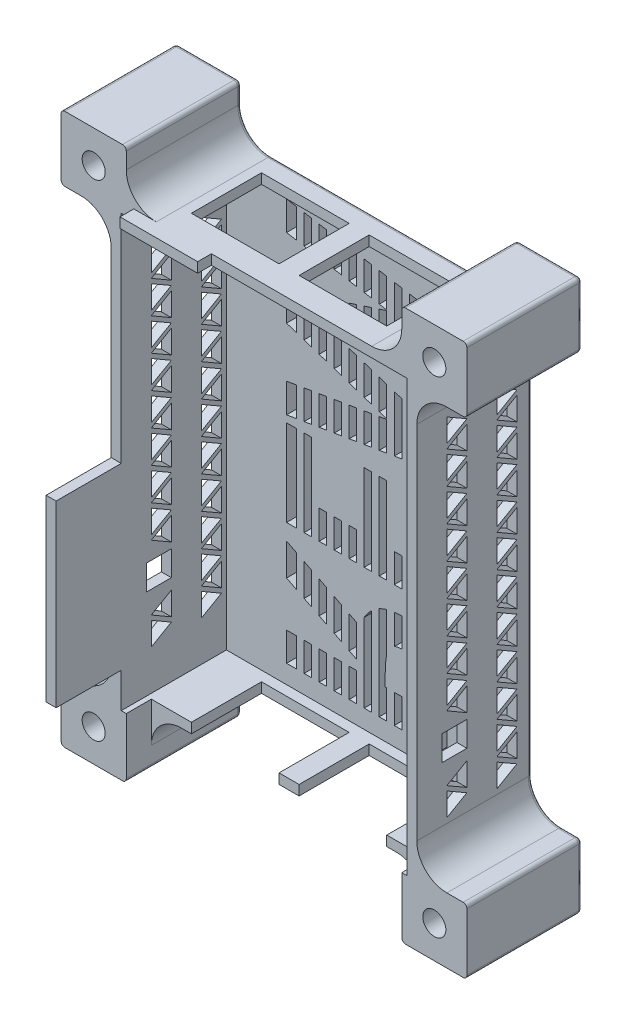
SolidWorks part; units mm, degrees
ref_plane "Front Plane" through (0, 0, 0) normal (0, 0, 1) x (1, 0, 0)
ref_plane "Top Plane" through (0, 0, 0) normal (0, 1, 0) x (1, 0, 0)
ref_plane "Right Plane" through (0, 0, 0) normal (1, 0, 0) x (0, 0, -1)
sketch "Sketch1" plane through (0, 0, 0) normal (0, 0, 1) x (1, 0, 0)
  line L1 (0, 0) -> (61, 0)
  line L2 (0, 0) -> (0, 90)
  line L3 (0, 90) -> (61, 90)
  line L4 (61, 0) -> (61, 90)
  dimension "D1" = 90
  dimension "D2" = 61
extrude "Boss-Extrude1" add sketch "Sketch1" along normal blind 4
sketch "Sketch2" plane through (0, 0, 4) normal (0, 0, 1) x (1, 0, 0)
  line L0 (61, 90) -> (0, 90) construction
  line L1 (2, 88) -> (59, 88)
  line L2 (2, 88) -> (2, 2)
  line L3 (2, 2) -> (59, 2)
  line L4 (59, 88) -> (59, 2)
  line L5 (2.2, 0) -> (-2.2, 0) construction
  line L6 (0, -2.2) -> (0, 2.2) construction
  line L7 (61, 0) -> (61, 90) construction
  dimension "D1" = 2
  dimension "D2" = 2
  dimension "D3" = 2
  dimension "D4" = 2
extrude "Cut-Extrude1" cut sketch "Sketch2" against normal blind 2
sketch "Sketch3" plane through (0, 0, 4) normal (0, 0, 1) x (1, 0, 0)
  line L8 (2, 88) -> (2, 2)
  line L9 (2, 2) -> (59, 2)
  line L10 (59, 2) -> (59, 88)
  line L11 (59, 88) -> (2, 88)
  line L12 (2, 88) -> (2, 2)
  line L13 (2, 2) -> (59, 2)
  line L14 (59, 2) -> (59, 88)
  line L15 (59, 88) -> (2, 88)
  line L26 (0, 90) -> (0, 0)
  line L27 (0, 0) -> (61, 0)
  line L28 (61, 0) -> (61, 90)
  line L29 (61, 90) -> (0, 90)
  line L30 (0, 90) -> (0, 0)
  line L31 (0, 0) -> (61, 0)
  line L32 (61, 0) -> (61, 90)
  line L33 (61, 90) -> (0, 90)
  dimension "D1" = 2
  dimension "D2" = 0
extrude "Boss-Extrude2" add sketch "Sketch3" along normal blind 14
sketch "Sketch4" plane through (0, 0, 18) normal (0, 0, 1) x (1, 0, 0)
  line L2 (9.9, 0) -> (-9.9, 0) construction
  line L3 (0, -9.9) -> (0, 9.9) construction
  line L4 (61, 0) -> (61, 90) construction
  line L10 (0, 90) -> (0, 0) construction
  line L12 (2, 88) -> (2, 2) construction
  line L13 (2, 88) -> (2, 2) construction
  line L14 (2, 2) -> (2, 88)
  line L15 (59, 88) -> (2, 88) construction
  line L16 (59, 88) -> (2, 88) construction
  line L49 (59, 88) -> (2, 88)
  line L50 (59, 2) -> (59, 88)
  line L52 (0, 90) -> (0, 2)
  line L53 (61, 90) -> (0, 90)
  line L54 (61, 2) -> (61, 90)
  line L55 (59, 2) -> (61, 2)
  line L56 (2, 2) -> (0, 2)
  dimension "D2" = 2
  dimension "D3" = 2
  dimension "D1" = 2
extrude "Boss-Extrude3" add sketch "Sketch4" along normal blind 5
sketch "Sketch5" plane through (0, 0, 0) normal (0, -1, 0) x (-1, 0, 0)
  line L0 (0, -18) -> (-61, -18) construction
  line L1 (-11, -18) -> (-28.5, -18)
  line L2 (-11, -18) -> (-11, -4)
  line L3 (-11, -4) -> (-28.5, -4)
  line L4 (-28.5, -18) -> (-28.5, -4)
  line L5 (0, 9.9) -> (0, -9.9) construction
  line L6 (-32.5, -18) -> (-50, -18)
  line L7 (-32.5, -18) -> (-32.5, -4)
  line L8 (-32.5, -4) -> (-50, -4)
  line L9 (-50, -18) -> (-50, -4)
  dimension "D1" = 14
  dimension "D2" = 14
  dimension "D3" = 17.5
  dimension "D4" = 17.5
  dimension "D5" = 4
  dimension "D6" = 11
extrude "Cut-Extrude2" cut sketch "Sketch5" against normal blind 5
sketch "Sketch6" plane through (0, 90, 0) normal (0, 1, 0) x (1, 0, 0)
  line L2 (50, -18) -> (50, -4)
  line L3 (50, -4) -> (32.5, -4)
  line L4 (32.5, -18) -> (32.5, -4)
  line L5 (61, 0) -> (0, 0) construction
  line L7 (28.5, -18) -> (28.5, -4)
  line L8 (28.5, -4) -> (11, -4)
  line L9 (11, -18) -> (11, -4)
  line L10 (61, -23) -> (61, 0) construction
  line L12 (11, -18) -> (28.5, -18)
  line L13 (32.5, -18) -> (50, -18)
  dimension "D1" = 4
  dimension "D2" = 4
  dimension "D3" = 4
  dimension "D4" = 17.5
  dimension "D5" = 17.5
  dimension "D6" = 11
  dimension "D7" = 14
  dimension "D8" = 14
extrude "Cut-Extrude3" cut sketch "Sketch6" against normal blind 5
sketch "Sketch7" plane through (0, 0, 23) normal (0, 0, 1) x (1, 0, 0)
  line L0 (0, 90) -> (0, 2) construction
  line L1 (0, 9) -> (2, 9)
  line L2 (0, 9) -> (0, 44.75)
  line L3 (0, 44.75) -> (2, 44.75)
  line L4 (2, 9) -> (2, 44.75)
  line L5 (2, 2) -> (2, 88) construction
  line L6 (0, 2) -> (2, 2) construction
  dimension "D1" = 7
  dimension "D2" = 35.75
extrude "Boss-Extrude4" add sketch "Sketch7" along normal blind 13
sketch "Sketch8" plane through (61, 0, 0) normal (1, 0, 0) x (0, 0, -1)
  line L0 (-13, 17.852) -> (-13, 13.2332)
  line L5 (-13, 13.2332) -> (-17, 15.5426)
  line L6 (-17, 15.5426) -> (-13, 17.852)
  line L8 (-13, 20) -> (-18, 20)
  line L9 (-13, 20) -> (-13, 25)
  line L10 (-13, 25) -> (-18, 25)
  line L11 (-18, 20) -> (-18, 25)
  line L23 (-18, 0) -> (0, 0) construction
  line L24 (0, 0) -> (0, 90) construction
  line L25 (-3, 12.3094) -> (-7, 10)
  line L26 (-7, 10) -> (-7, 14.6188)
  line L27 (-7, 14.6188) -> (-3, 12.3094)
  line L28 (-3, 13.2332) -> (-7, 15.5426)
  line L29 (-7, 15.5426) -> (-3, 17.852)
  line L30 (-3, 17.852) -> (-3, 13.2332)
  line L31 (-17, 14.6188) -> (-13, 12.3094)
  line L32 (-13, 12.3094) -> (-17, 10)
  line L33 (-17, 10) -> (-17, 14.6188)
  line L40 (-13, 30.7846) -> (-13, 26.1658)
  line L41 (-13, 26.1658) -> (-17, 28.4752)
  line L42 (-17, 28.4752) -> (-13, 30.7846)
  line L46 (-13, 37.2509) -> (-13, 32.6321)
  line L47 (-13, 32.6321) -> (-17, 34.9415)
  line L48 (-17, 34.9415) -> (-13, 37.2509)
  line L49 (-17, 34.0178) -> (-13, 31.7084)
  line L50 (-13, 31.7084) -> (-17, 29.399)
  line L51 (-17, 29.399) -> (-17, 34.0178)
  line L52 (-13, 43.7173) -> (-13, 39.0985)
  line L53 (-13, 39.0985) -> (-17, 41.4079)
  line L54 (-17, 41.4079) -> (-13, 43.7173)
  line L55 (-17, 40.4841) -> (-13, 38.1747)
  line L56 (-13, 38.1747) -> (-17, 35.8653)
  line L57 (-17, 35.8653) -> (-17, 40.4841)
  line L58 (-13, 50.1836) -> (-13, 45.5648)
  line L59 (-13, 45.5648) -> (-17, 47.8742)
  line L60 (-17, 47.8742) -> (-13, 50.1836)
  line L61 (-17, 46.9504) -> (-13, 44.641)
  line L62 (-13, 44.641) -> (-17, 42.3316)
  line L63 (-17, 42.3316) -> (-17, 46.9504)
  line L64 (-13, 56.6499) -> (-13, 52.0311)
  line L65 (-13, 52.0311) -> (-17, 54.3405)
  line L66 (-17, 54.3405) -> (-13, 56.6499)
  line L67 (-17, 53.4167) -> (-13, 51.1073)
  line L68 (-13, 51.1073) -> (-17, 48.7979)
  line L69 (-17, 48.7979) -> (-17, 53.4167)
  line L70 (-13, 63.1162) -> (-13, 58.4974)
  line L71 (-13, 58.4974) -> (-17, 60.8068)
  line L72 (-17, 60.8068) -> (-13, 63.1162)
  line L73 (-17, 59.8831) -> (-13, 57.5737)
  line L74 (-13, 57.5737) -> (-17, 55.2643)
  line L75 (-17, 55.2643) -> (-17, 59.8831)
  line L76 (-13, 69.5825) -> (-13, 64.9637)
  line L77 (-13, 64.9637) -> (-17, 67.2731)
  line L78 (-17, 67.2731) -> (-13, 69.5825)
  line L79 (-17, 66.3494) -> (-13, 64.04)
  line L80 (-13, 64.04) -> (-17, 61.7306)
  line L81 (-17, 61.7306) -> (-17, 66.3494)
  line L82 (-13, 76.0489) -> (-13, 71.4301)
  line L83 (-13, 71.4301) -> (-17, 73.7395)
  line L84 (-17, 73.7395) -> (-13, 76.0489)
  line L85 (-17, 72.8157) -> (-13, 70.5063)
  line L86 (-13, 70.5063) -> (-17, 68.1969)
  line L87 (-17, 68.1969) -> (-17, 72.8157)
  line L91 (-17, 79.282) -> (-13, 76.9726)
  line L92 (-13, 76.9726) -> (-17, 74.6632)
  line L93 (-17, 74.6632) -> (-17, 79.282)
  line L94 (-3, 24.3183) -> (-3, 19.6995)
  line L95 (-3, 19.6995) -> (-7, 22.0089)
  line L96 (-7, 22.0089) -> (-3, 24.3183)
  line L97 (-7, 21.0851) -> (-3, 18.7757)
  line L98 (-3, 18.7757) -> (-7, 16.4663)
  line L99 (-7, 16.4663) -> (-7, 21.0851)
  line L100 (-3, 30.7846) -> (-3, 26.1658)
  line L101 (-3, 26.1658) -> (-7, 28.4752)
  line L102 (-7, 28.4752) -> (-3, 30.7846)
  line L103 (-7, 27.5514) -> (-3, 25.242)
  line L104 (-3, 25.242) -> (-7, 22.9326)
  line L105 (-7, 22.9326) -> (-7, 27.5514)
  line L106 (-3, 37.2509) -> (-3, 32.6321)
  line L107 (-3, 32.6321) -> (-7, 34.9415)
  line L108 (-7, 34.9415) -> (-3, 37.2509)
  line L109 (-7, 34.0178) -> (-3, 31.7084)
  line L110 (-3, 31.7084) -> (-7, 29.399)
  line L111 (-7, 29.399) -> (-7, 34.0178)
  line L112 (-3, 43.7173) -> (-3, 39.0985)
  line L113 (-3, 39.0985) -> (-7, 41.4079)
  line L114 (-7, 41.4079) -> (-3, 43.7173)
  line L115 (-7, 40.4841) -> (-3, 38.1747)
  line L116 (-3, 38.1747) -> (-7, 35.8653)
  line L117 (-7, 35.8653) -> (-7, 40.4841)
  line L118 (-3, 50.1836) -> (-3, 45.5648)
  line L119 (-3, 45.5648) -> (-7, 47.8742)
  line L120 (-7, 47.8742) -> (-3, 50.1836)
  line L121 (-7, 46.9504) -> (-3, 44.641)
  line L122 (-3, 44.641) -> (-7, 42.3316)
  line L123 (-7, 42.3316) -> (-7, 46.9504)
  line L124 (-3, 56.6499) -> (-3, 52.0311)
  line L125 (-3, 52.0311) -> (-7, 54.3405)
  line L126 (-7, 54.3405) -> (-3, 56.6499)
  line L127 (-7, 53.4167) -> (-3, 51.1073)
  line L128 (-3, 51.1073) -> (-7, 48.7979)
  line L129 (-7, 48.7979) -> (-7, 53.4167)
  line L130 (-3, 63.1162) -> (-3, 58.4974)
  line L131 (-3, 58.4974) -> (-7, 60.8068)
  line L132 (-7, 60.8068) -> (-3, 63.1162)
  line L133 (-7, 59.8831) -> (-3, 57.5737)
  line L134 (-3, 57.5737) -> (-7, 55.2643)
  line L135 (-7, 55.2643) -> (-7, 59.8831)
  line L136 (-3, 69.5825) -> (-3, 64.9637)
  line L137 (-3, 64.9637) -> (-7, 67.2731)
  line L138 (-7, 67.2731) -> (-3, 69.5825)
  line L139 (-7, 66.3494) -> (-3, 64.04)
  line L140 (-3, 64.04) -> (-7, 61.7306)
  line L141 (-7, 61.7306) -> (-7, 66.3494)
  line L142 (-3, 76.0489) -> (-3, 71.4301)
  line L143 (-3, 71.4301) -> (-7, 73.7395)
  line L144 (-7, 73.7395) -> (-3, 76.0489)
  line L145 (-7, 72.8157) -> (-3, 70.5063)
  line L146 (-3, 70.5063) -> (-7, 68.1969)
  line L147 (-7, 68.1969) -> (-7, 72.8157)
  line L151 (-7, 79.282) -> (-3, 76.9726)
  line L152 (-3, 76.9726) -> (-7, 74.6632)
  line L153 (-7, 74.6632) -> (-7, 79.282)
  line L154 (-13, 18.7757) -> (-17, 16.4663) [skipped]
  line L155 (-17, 21.0851) -> (-15.1205, 20) [skipped]
  line L156 (-17, 20) -> (-17, 21.0851) [skipped]
  line L157 (-17, 22.0089) -> (-13, 24.3183) [skipped]
  line L158 (-13, 19.6995) -> (-13.5205, 20) [skipped]
  line L159 (-17, 27.5514) -> (-13, 25.242) [skipped]
  line L160 (-13, 25.242) -> (-13.4192, 25) [skipped]
  line L161 (-17, 25) -> (-17, 27.5514) [skipped]
  line L162 (-13, 18.7757) -> (-13, 17.5514) [skipped]
  line L163 (-13, 82.5152) -> (-13, 77.8964) [skipped]
  line L164 (-17, 80.2058) -> (-13, 82.5152) [skipped]
  line L165 (-13, 77.8964) -> (-17, 80.2058) [skipped]
  line L166 (-7, 80.2058) -> (-3, 82.5152) [skipped]
  line L167 (-3, 77.8964) -> (-7, 80.2058) [skipped]
  line L168 (-3, 82.5152) -> (-3, 77.8964) [skipped]
  point P7 (-13, 18.7757)
  dimension "D1" = 20
  dimension "D2" = 60
  dimension "D3" = 60
  dimension "D4" = 4
  dimension "D5" = 5
  dimension "D6" = 5
  dimension "D7" = 13
  dimension "D8" = 0.9238
  dimension "D9" = 10
  dimension "D10" = 3
  dimension "D11" = 60
  dimension "D12" = 2
  dimension "D13" = 11
  dimension "D14" = 0.9238
  dimension "D15" = 17
extrude "Cut-Extrude4" cut sketch "Sketch8" against normal through all
sketch "Sketch9" plane through (-13.2665, 62.4944, 0) normal (0, 0, -1) x (0, 1, 0)
  line L2 (-42.6944, 13.2665) -> (-82.2944, 13.2665) construction
  line L3 (-62.4944, -6.5335) -> (-62.4944, 33.0665) construction
  text T0 "REM" font "Century Gothic" height 32
  dimension "D1" = 14
  dimension "D2" = 2
extrude "Cut-Extrude5" cut sketch "Sketch9" against normal blind 2
sketch "Sketch16" plane through (0, 0, 23) normal (0, 0, 1) x (1, 0, 0)
  line L0 (2, 88) -> (59, 88) construction
  line L1 (20, 88) -> (4.5, 88)
  line L2 (20, 88) -> (20, 90)
  line L3 (20, 90) -> (4.5, 90)
  line L4 (4.5, 88) -> (4.5, 90)
  line L5 (61, 90) -> (0, 90) construction
  line L6 (0, 90) -> (0, 61) construction
  dimension "D1" = 4.5
  dimension "D2" = 15.5
extrude "Boss-Extrude9" add sketch "Sketch16" along normal blind 2.75
ref_plane "Plane1" through (2, 14.6188, 17) normal (0, 1, 0) x (1, 0, 0)
sketch "Sketch22" plane through (0, 0, 0) normal (0, 0, -1) x (-1, 0, 0)
  line L0 (-14, 85.9795) -> (-14, 80.1654) construction
  line L1 (-26.5, 0) -> (-25, 0)
  line L2 (0, 0) -> (-61, 0) construction
  line L3 (-61, 90) -> (0, 90) construction
  line L4 (-28, 0) -> (-28, 90)
  line L5 (-28, 90) -> (-29.5, 90)
  line L6 (-29.5, 90) -> (-29.5, 0)
  line L7 (-29.5, 0) -> (-28, 0)
  line L8 (-25, 0) -> (-25, 90)
  line L9 (-25, 90) -> (-26.5, 90)
  line L10 (-26.5, 90) -> (-26.5, 0)
  line L11 (-23.5, 0) -> (-22, 0)
  line L12 (-22, 0) -> (-22, 90)
  line L13 (-22, 90) -> (-23.5, 90)
  line L14 (-23.5, 90) -> (-23.5, 0)
  line L15 (-20.5, 0) -> (-19, 0)
  line L16 (-19, 0) -> (-19, 90)
  line L17 (-19, 90) -> (-20.5, 90)
  line L18 (-20.5, 90) -> (-20.5, 0)
  line L19 (-17.5, 0) -> (-16, 0)
  line L20 (-16, 0) -> (-16, 90)
  line L21 (-16, 90) -> (-17.5, 90)
  line L22 (-17.5, 90) -> (-17.5, 0)
  line L23 (-32.5, 0) -> (-31, 0)
  line L24 (-31, 0) -> (-31, 90)
  line L25 (-31, 90) -> (-32.5, 90)
  line L26 (-32.5, 90) -> (-32.5, 0)
  line L27 (-35.5, 0) -> (-34, 0)
  line L28 (-34, 0) -> (-34, 90)
  line L29 (-34, 90) -> (-35.5, 90)
  line L30 (-35.5, 90) -> (-35.5, 0)
  line L31 (-38.5, 0) -> (-37, 0)
  line L32 (-37, 0) -> (-37, 90)
  line L33 (-37, 90) -> (-38.5, 90)
  line L34 (-38.5, 90) -> (-38.5, 0)
  line L35 (-41.5, 0) -> (-40, 0)
  line L36 (-40, 0) -> (-40, 90)
  line L37 (-40, 90) -> (-41.5, 90)
  line L38 (-41.5, 90) -> (-41.5, 0)
  line L39 (-44.5, 0) -> (-43, 0)
  line L40 (-43, 0) -> (-43, 90)
  line L41 (-43, 90) -> (-44.5, 90)
  line L42 (-44.5, 90) -> (-44.5, 0)
  line L43 (-47.5, 0) -> (-46, 0)
  line L44 (-46, 0) -> (-46, 90)
  line L45 (-46, 90) -> (-47.5, 90)
  line L46 (-47.5, 90) -> (-47.5, 0)
  line L47 (-50.5, 0) -> (-49, 0)
  line L48 (-49, 0) -> (-49, 90)
  line L49 (-49, 90) -> (-50.5, 90)
  line L50 (-50.5, 90) -> (-50.5, 0)
  dimension "D2" = 1.5
  dimension "D4" = 1.5
  dimension "D6" = 1.5
  dimension "D1" = 2
  dimension "D3" = 5
  dimension "D5" = 8
extrude "Boss-Extrude11" add sketch "Sketch22" against normal up to surface (2 mm away) up to face at (36.3205, 13.9436, 2)
fillet "Fillet5" radius 0.75 8 edges at (30.5, 90, 0) (0, 90, 11.5) (30.5, 0, 0) (0, 45, 0) (0, 0, 9) (61, 90, 11.5) (61, 0, 9) (61, 45, 0)
sketch "Sketch36" plane through (0, 0, 0) normal (0, 0, -1) x (-1, 0, 0)
  line L0 (-61, 0.75) -> (-61, 89.25) construction
  line L1 (-58, 3) -> (-71, 3)
  line L2 (-58, 3) -> (-58, -10)
  line L3 (-58, -10) -> (-71, -10)
  line L4 (-71, 3) -> (-71, -10)
  line L5 (-58, 3) -> (-71, -10) construction
  line L6 (-58, -10) -> (-71, 3) construction
  line L8 (-0.75, 0) -> (-60.25, 0) construction
  point P4 (-64.5, -3.5)
  dimension "D1" = 13
  dimension "D2" = 13
  dimension "D3" = 3
  dimension "D4" = 3
extrude "Boss-Extrude13" add sketch "Sketch36" against normal up to surface (23 mm away) up to face at (48.6293, 64.2008, 23)
sketch "Sketch37" plane through (0, 0, 0) normal (0, 0, -1) x (-1, 0, 0)
  line L0 (-60.25, 90) -> (-0.75, 90) construction
  line L1 (-3, 87) -> (10, 87)
  line L2 (-3, 87) -> (-3, 100)
  line L3 (-3, 100) -> (10, 100)
  line L4 (10, 87) -> (10, 100)
  line L5 (-3, 87) -> (10, 100) construction
  line L6 (-3, 100) -> (10, 87) construction
  line L7 (0, 89.25) -> (0, 0.75) construction
  point P4 (3.5, 93.5)
  dimension "D1" = 13
  dimension "D2" = 3
  dimension "D3" = 3
extrude "Boss-Extrude14" add sketch "Sketch37" against normal up to surface (23 mm away) up to face at (1.9421, 76.415, 23)
sketch "Sketch41" plane through (0, 0, 23) normal (0, 0, 1) x (1, 0, 0)
  line L9 (58, 3) -> (59, 3)
  line L10 (58, 3) -> (58, 2)
  line L11 (58, 2) -> (59, 2)
  line L12 (59, 3) -> (59, 2)
  line L13 (58, 3) -> (59, 2) construction
  line L14 (58, 2) -> (59, 3) construction
  line L15 (3, 87) -> (2, 87)
  line L16 (3, 87) -> (3, 88)
  line L17 (3, 88) -> (2, 88)
  line L18 (2, 87) -> (2, 88)
  line L19 (3, 87) -> (2, 88) construction
  line L20 (3, 88) -> (2, 87) construction
  point P13 (58.5, 2.5)
  point P15 (2.5, 87.5)
  dimension "D1" = 1
  dimension "D2" = 1
  dimension "D3" = 1
  dimension "D4" = 1
extrude "Cut-Extrude13" cut sketch "Sketch41" against normal up to surface (21 mm away) up to face at (30.5, 45, 2)
sketch "Sketch46" plane through (0, 0, 0) normal (0, 0, -1) x (-1, 0, 0)
  line L0 (3.5, 100) -> (3.5, 87) construction
  line L1 (10, 100) -> (-3, 100) construction
  line L2 (-0.75, 87) -> (10, 87) construction
  line L3 (10, 93.5) -> (-3, 93.5) construction
  line L4 (10, 87) -> (10, 100) construction
  line L5 (-71, -3.5) -> (-58, -3.5) construction
  line L6 (-71, 3) -> (-71, -10) construction
  line L7 (-58, -10) -> (-58, 0.75) construction
  line L8 (-64.5, -10) -> (-64.5, 3) construction
  line L9 (-71, -10) -> (-58, -10) construction
  line L10 (-60.25, 3) -> (-71, 3) construction
  line L11 (-3, 100) -> (-3, 89.25) construction
  circle A0 centre (-64.5, -3.5) radius 2.3
  circle A1 centre (3.5, 93.5) radius 2.3
  dimension "D1" = 4.6
  dimension "D2" = 4.6
sketch "Sketch49" plane through (0, 0, 0) normal (0, 0, -1) x (-1, 0, 0)
  line L0 (-60.25, 89.25) -> (-60.25, 3) construction
  line L1 (-61, 3) -> (-60.25, 3)
  line L2 (-61, 3) -> (-61, 90)
  line L3 (-61, 90) -> (-60.25, 90)
  line L4 (-60.25, 3) -> (-60.25, 90)
  line L5 (-61, 3) -> (-60.25, 90) construction
  line L6 (-61, 90) -> (-60.25, 3) construction
  line L7 (-60.25, 90) -> (-3, 90)
  line L8 (-60.25, 90) -> (-60.25, 89.25)
  line L9 (-60.25, 89.25) -> (-3, 89.25)
  line L10 (-3, 90) -> (-3, 89.25)
  line L11 (-60.25, 90) -> (-3, 89.25) construction
  line L12 (-60.25, 89.25) -> (-3, 90) construction
  line L13 (-0.75, 87) -> (0, 87)
  line L14 (-0.75, 87) -> (-0.75, 0)
  line L15 (-0.75, 0) -> (0, 0)
  line L16 (0, 87) -> (0, 0)
  line L17 (-0.75, 87) -> (0, 0) construction
  line L18 (-0.75, 0) -> (0, 87) construction
  line L19 (-0.75, 0) -> (-58, 0)
  line L20 (-0.75, 0) -> (-0.75, 0.75)
  line L21 (-0.75, 0.75) -> (-58, 0.75)
  line L22 (-58, 0) -> (-58, 0.75)
  line L23 (-0.75, 0) -> (-58, 0.75) construction
  line L24 (-0.75, 0.75) -> (-58, 0) construction
  arc A0 (-60.25, 90) -> (-61, 89.25) centre (-60.25, 89.25) ccw construction
  point P4 (-60.625, 46.5)
  point P12 (-31.625, 89.625)
  point P18 (-0.375, 43.5)
  point P24 (-29.375, 0.375)
extrude "Boss-Extrude15" add sketch "Sketch49" against normal blind 1 contours L2 L1 L4 L3 | L20 L19 L22 L21 | L14 L13 L16 L15 | L8 L7 L10 L9
fillet "Fillet8" radius 6 1 edges at (61, 3, 11.5) type face fillet first side face at (61, 73.7395, 14.3333) second side face at (66, 3, 11.5) tangent propagation no
fillet "Fillet9" radius 6 1 edges at (58, 0, 9) type face fillet first side face at (58, -2.6667, 13.6667) second side face at (25.8214, 0, 9) tangent propagation no
fillet "Fillet10" radius 6 1 edges at (3, 90, 11.5) type face fillet first side face at (29.75, 90, 14.55) second side face at (3, 95, 11.5) tangent propagation no
fillet "Fillet11" radius 6 1 edges at (0, 87, 11.5) type face fillet first side face at (0, 73.7395, 14.3333) second side face at (-5, 87, 11.5) tangent propagation no
extrude "Cut-Extrude18" cut sketch "Sketch46" against normal through all
sketch "Sketch50" plane through (0, 90, 0) normal (0, 1, 0) x (1, 0, 0)
  line L0 (20, -25.75) -> (9, -25.75) construction
  line L1 (4.5, -23) -> (10, -23)
  line L2 (4.5, -23) -> (4.5, -25.75)
  line L3 (4.5, -25.75) -> (10, -25.75)
  line L4 (10, -23) -> (10, -25.75)
  line L5 (4.5, -23) -> (10, -25.75) construction
  line L6 (4.5, -25.75) -> (10, -23) construction
  point P4 (7.25, -24.375)
  dimension "D1" = 5.5
extrude "Cut-Extrude19" cut sketch "Sketch50" along normal through all
sketch "Sketch51" plane through (0, 0, 23) normal (0, 0, 1) x (1, 0, 0)
  line L0 (61, 9) -> (61, 89.25) construction
  line L1 (-10, -10) -> (3, -10)
  line L2 (-10, -10) -> (-10, 3)
  line L3 (-10, 3) -> (2, 3)
  line L4 (3, -10) -> (3, 2)
  line L5 (-10, -10) -> (2, 2) construction
  line L6 (-10, 3) -> (3, -10) construction
  line L7 (59, 87) -> (71, 87)
  line L8 (58, 88) -> (58, 100)
  line L9 (58, 100) -> (71, 100)
  line L10 (71, 87) -> (71, 100)
  line L11 (59, 88) -> (71, 100) construction
  line L12 (58, 100) -> (71, 87) construction
  line L13 (60.25, 90) -> (20, 90) construction
  line L14 (0.75, 0) -> (11, 0) construction
  line L15 (0, 44.75) -> (0, 9) construction
  line L16 (2, 2) -> (11, 2) construction
  line L17 (2, 2) -> (2, 9) construction
  line L18 (2, 2) -> (3, 2)
  line L19 (2, 2) -> (2, 3)
  line L20 (59, 88) -> (59, 2) construction
  line L21 (59, 88) -> (2, 88) construction
  line L22 (59, 88) -> (59, 87)
  line L23 (59, 88) -> (58, 88)
  point P4 (-3.5, -3.5)
  point P9 (64.5, 93.5)
  dimension "D1" = 3
  dimension "D2" = 3
  dimension "D3" = 3
  dimension "D4" = 3
  dimension "D5" = 13
  dimension "D6" = 13
  dimension "D7" = 13
  dimension "D8" = 13
extrude "Boss-Extrude16" add sketch "Sketch51" against normal up to surface (23 mm away) contours L1 L4 L18 L19 L3 L2 | L7 L10 L9 L8 L23 L22 up to face at (62.2, -3.5, 0)
sketch "Sketch52" plane through (0, 0, 0) normal (0, 0, -1) x (-1, 0, 0)
  line L0 (-64.5, 100) -> (-64.5, 87) construction
  line L1 (-58, 100) -> (-71, 100) construction
  line L2 (-61, 87) -> (-71, 87) construction
  line L3 (-71, 93.5) -> (-58, 93.5) construction
  line L4 (-71, 87) -> (-71, 100) construction
  line L5 (-58, 90) -> (-58, 100) construction
  line L6 (3.5, -10) -> (3.5, 3) construction
  line L7 (10, -10) -> (-3, -10) construction
  line L8 (10, 3) -> (0, 3) construction
  line L9 (10, -3.5) -> (-3, -3.5) construction
  line L10 (10, -10) -> (10, 3) construction
  line L11 (-3, -10) -> (-3, 0) construction
  circle A0 centre (-64.5, 93.5) radius 2.3
  circle A1 centre (3.5, -3.5) radius 2.3
  dimension "D1" = 4.6
  dimension "D2" = 4.6
extrude "Cut-Extrude20" cut sketch "Sketch52" against normal through all
fillet "Fillet13" radius 6 1 edges at (58, 90, 11.5) type face fillet first side face at (58, 95, 11.5) second side face at (41.25, 90, 11) tangent propagation no
fillet "Fillet14" radius 6 1 edges at (61, 87, 11.5) type face fillet first side face at (66, 87, 11.5) second side face at (61, 73.7395, 14.3333) tangent propagation no
fillet "Fillet15" radius 6 1 edges at (3, 0, 9) type face fillet first side face at (29.5, 0, 10.3333) second side face at (3, -2.6667, 13.6667) tangent propagation no
fillet "Fillet16" radius 6 1 edges at (0, 3, 11.5) type face fillet first side face at (-5, 3, 11.5) second side face at (0, 12.3094, 5.6667) tangent propagation no
fillet "Fillet18" radius 0.75 40 edges at (58, 98, 0) (56.2426, 91.7574, 0) (30.5, 90, 0) (3, 98, 0) (-8, 87, 0) (-1.7574, 85.2426, 0) (-8, 3, 0) (-1.7574, 4.7574, 0) (69, 3, 0) (69, 87, 0) (62.7574, 85.2426, 0) (61, 45, 0) (3, -8, 0) (4.7574, -1.7574, 0) (30.5, 0, 0) (58, -8, 0) (3, 100, 11.5) (71, 87, 11.5) (71, 100, 11.5) (58, 100, 11.5) (71, 3, 11.5) (4.7574, 91.7574, 0) (-3.5, 100, 0) (-10, 100, 11.5) (-10, 93.5, 0) (-10, 87, 11.5) (0, 45, 0) (-10, 3, 11.5) (-10, -3.5, 0) (-3.5, -10, 0) (-10, -10, 11.5) (3, -10, 11.5) (58, -10, 11.5) (71, -10, 11.5) (64.5, -10, 0) (71, -3.5, 0) (62.7574, 4.7574, 0) (56.2426, -1.7574, 0) (71, 93.5, 0) (64.5, 100, 0)
equation "\"A\"= 1.5mm"
equation "\"B\"= 1.5mm"
equation "\"D2@Sketch22\"=\"A\""
